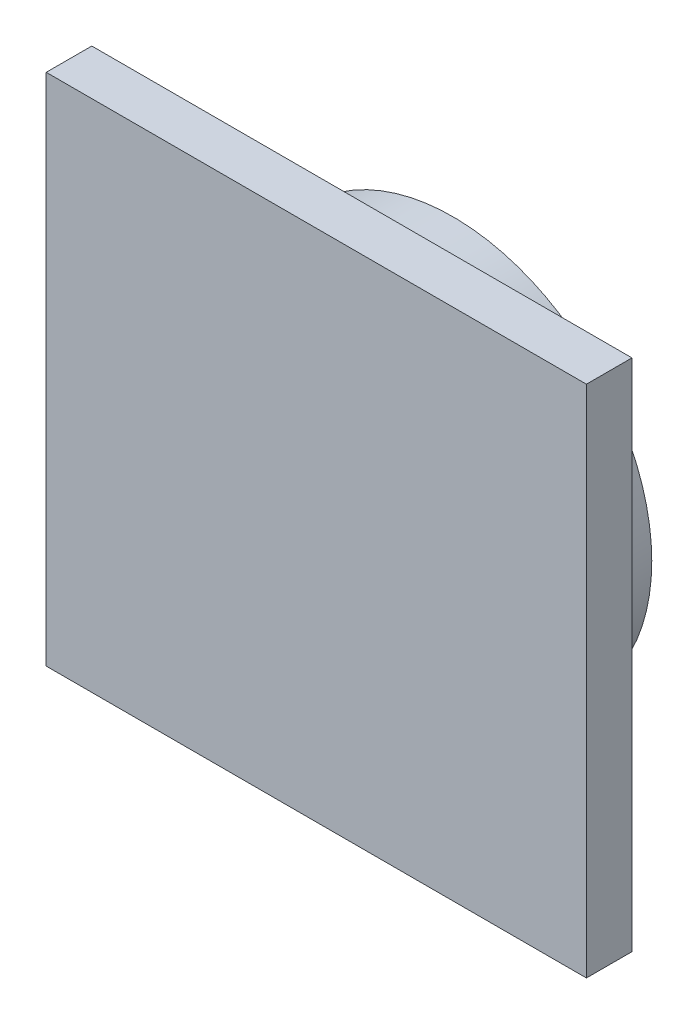
SolidWorks part; units mm, degrees
ref_plane "Front Plane" through (0, 0, 0) normal (0, 0, 1) x (1, 0, 0)
ref_plane "Top Plane" through (0, 0, 0) normal (0, 1, 0) x (1, 0, 0)
ref_plane "Right Plane" through (0, 0, 0) normal (1, 0, 0) x (0, 0, -1)
sketch "Sketch1" plane through (0, 0, 0) normal (0, 0, 1) x (1, 0, 0)
  circle A0 centre (0, 0) radius 43.6326
extrude "Boss-Extrude1" add sketch "Sketch1" along normal blind 10
sketch "Sketch2" plane through (0, 0, 10) normal (0, 0, 1) x (1, 0, 0)
  circle A0 centre (0, 0) radius 18.0827
extrude "Cut-Extrude1" cut sketch "Sketch2" against normal up to surface (10 mm away) up to face at (43.6326, 0, 0)
sketch "Sketch3" plane through (0, 0, 10) normal (0, 0, 1) x (1, 0, 0)
  circle A0 centre (0, 0) radius 26.6286
extrude "Boss-Extrude2" add sketch "Sketch3" along normal blind 10
sketch "Sketch4" plane through (0, 0, 20) normal (0, 0, 1) x (1, 0, 0)
  line L1 (-59.2866, 56.4405) -> (59.2866, 56.4405)
  line L2 (-59.2866, 56.4405) -> (-59.2866, -56.4405)
  line L3 (-59.2866, -56.4405) -> (59.2866, -56.4405)
  line L4 (59.2866, 56.4405) -> (59.2866, -56.4405)
  line L5 (-59.2866, 56.4405) -> (59.2866, -56.4405) construction
  line L6 (-59.2866, -56.4405) -> (59.2866, 56.4405) construction
  point P0 (0, 0)
extrude "Boss-Extrude3" add sketch "Sketch4" along normal blind 10
